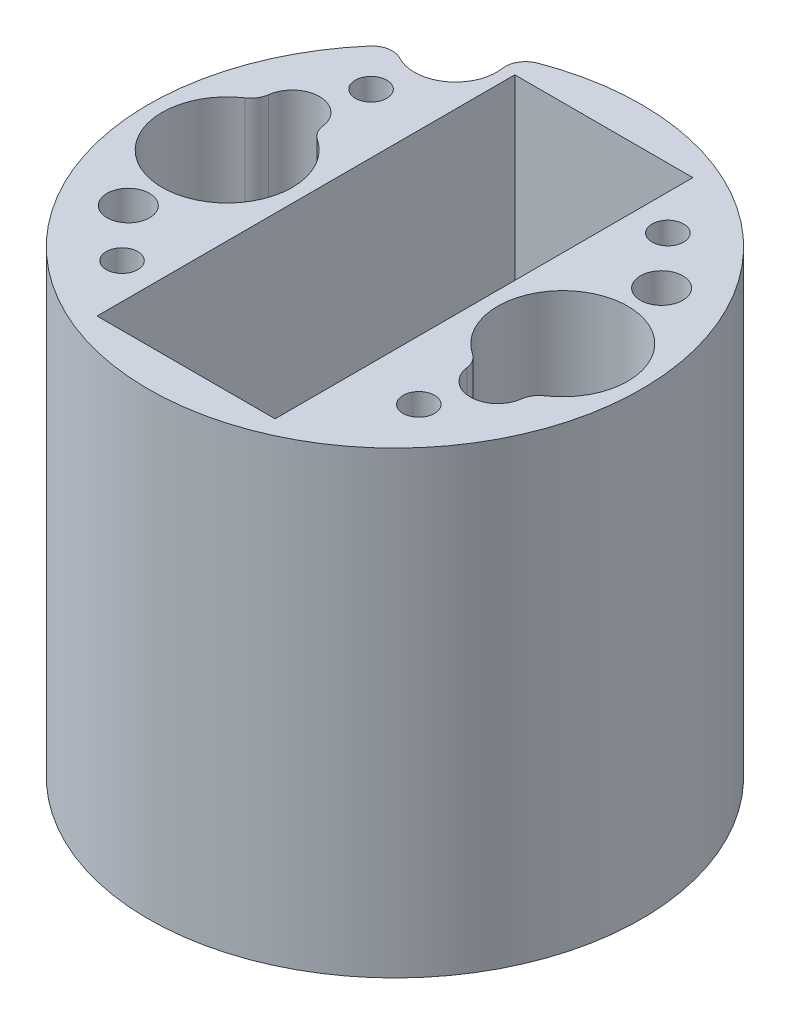
SolidWorks part; units mm, degrees
ref_plane "Front Plane" through (0, 0, 0) normal (0, 0, 1) x (1, 0, 0)
ref_plane "Top Plane" through (0, 0, 0) normal (0, 1, 0) x (1, 0, 0)
ref_plane "Right Plane" through (0, 0, 0) normal (1, 0, 0) x (0, 0, -1)
sketch "Sketch1" plane through (0, 0, 0) normal (0, 1, 0) x (1, 0, 0)
  line L0 (-13, 30.5) -> (13, -30.5) construction
  line L1 (-13, 30.5) -> (13, 30.5)
  line L2 (-13, 30.5) -> (-13, -30.5)
  line L3 (-13, -30.5) -> (13, -30.5)
  line L4 (13, 30.5) -> (13, -30.5)
  line L5 (-24.5, 0) -> (24.5, 0) construction
  line L6 (-34, 0) -> (-36, 0) construction
  line L7 (34, 0) -> (36, 0) construction
  line L8 (-15, 0) -> (-13, 0) construction
  circle A0 centre (0, 0) radius 36
  circle A3 centre (-24.5, 0) radius 9.5
  circle A4 centre (24.5, 0) radius 9.5
  point P5 (0, 0)
  point P12 (0, 0)
  dimension "D1" = 72
  dimension "D2" = 61
  dimension "D4" = 19
  dimension "D3" = 26
extrude "Boss-Extrude1" add sketch "Sketch1" along normal blind 64
sketch "Sketch2" plane through (0, 0, 0) normal (0, -1, 0) x (1, 0, 0)
  circle A0 centre (0, 0) radius 36
extrude "Boss-Extrude2" add sketch "Sketch2" along normal blind 3
extrude "Boss-Extrude3" add sketch "Sketch1<2>" along normal blind 16 contours A3 | A4 region at (-24.5, 0, 0) region at (24.5, 0, 0)
sketch "Sketch1<2>" plane through (0, 0, 0) normal (0, 1, 0) x (1, 0, 0) same geometry as "Sketch1"
sketch "Sketch4" plane through (0, 64, 0) normal (0, 1, 0) x (1, 0, 0)
  line L0 (-24.5, 9.5) -> (-24.5, 0) construction
  line L1 (-24.5, 0) -> (24.5, 0) construction
  line L2 (24.5, 0) -> (24.5, -9.5) construction
  line L3 (-24.5, 9.5) -> (-1.5428, 9.5) construction
  circle A0 centre (-24.5, 9.5) radius 4
  circle A1 centre (-24.5, 0) radius 9.5 construction
  circle A2 centre (-24.5, 0) radius 9.5 construction
  circle A3 centre (24.5, -9.5) radius 4
  circle A4 centre (24.5, 0) radius 9.5 construction
  circle A5 centre (24.5, 0) radius 9.5 construction
  dimension "D1" = 8
extrude "Cut-Extrude1" cut sketch "Sketch4" against normal up to surface (48 mm away) up to face at (-24.5, 16, 9.5)
sketch "Sketch5" plane through (0, 64, 0) normal (0, 1, 0) x (1, 0, 0)
  line L0 (0, 0) -> (20.0764, 0) construction
  line L1 (-18.1808, -21.667) -> (21.667, -18.1808) construction
  line L2 (-18.1808, -21.667) -> (-21.667, 18.1808) construction
  line L3 (-21.667, 18.1808) -> (18.1808, 21.667) construction
  line L4 (21.667, -18.1808) -> (18.1808, 21.667) construction
  line L5 (-18.1808, -21.667) -> (18.1808, 21.667) construction
  line L6 (-21.667, 18.1808) -> (21.667, -18.1808) construction
  circle A0 centre (-21.667, 18.1808) radius 1.5
  circle A1 centre (-18.1808, -21.667) radius 1.5
  circle A2 centre (21.667, -18.1808) radius 1.5
  circle A3 centre (18.1808, 21.667) radius 1.5
  circle A4 centre (-21.667, 18.1808) radius 2.3
  circle A5 centre (18.1808, 21.667) radius 2.3
  circle A6 centre (21.667, -18.1808) radius 2.3
  circle A7 centre (-18.1808, -21.667) radius 2.3
  point P0 (0, 0)
  dimension "D2" = 3
  dimension "D3" = 4.6
  dimension "D1" = 40
  dimension "D4" = 85
extrude "Cut-Extrude2" cut sketch "Sketch5" against normal blind 20 contours A0 | A3 | A1 | A2 region at (-21.667, 64, -18.1808) region at (-18.1808, 64, 21.667) region at (21.667, 64, 18.1808) region at (18.1808, 64, -21.667)
extrude "Cut-Extrude3" cut sketch "Sketch5<3>" against normal blind 6
sketch "Sketch5<3>" plane through (0, 64, 0) normal (0, 1, 0) x (1, 0, 0) same geometry as "Sketch5"
sketch "Sketch6" plane through (0, 64, 0) normal (0, 1, 0) x (1, 0, 0)
  line L0 (-24.6817, -14.25) -> (24.6817, 14.25) construction
  line L1 (0, 0) -> (24.909, 0) construction
  circle A0 centre (-24.6817, -14.25) radius 3.1
  circle A1 centre (24.6817, 14.25) radius 3.1
  point P4 (0, 0)
  dimension "D1" = 6.2
  dimension "D2" = 57
  dimension "D3" = 30
extrude "Cut-Extrude4" cut sketch "Sketch6" against normal through all both and the other way through all
sketch "Sketch7" plane through (0, 64, 0) normal (0, 1, 0) x (1, 0, 0)
  line L0 (-20.6488, 29.4895) -> (0, 0) construction
  line L1 (0, 0) -> (0, 21.7628) construction
  arc A0 (-25.2598, 25.6504) -> (-15.4641, 32.5094) centre (-20.6488, 29.4895) ccw
  circle A1 centre (0, 0) radius 36 construction
  arc A2 (-15.4641, 32.5094) -> (-25.2598, 25.6504) centre (0, 0) ccw
  dimension "D1" = 6
  dimension "D2" = 35
extrude "Cut-Extrude5" cut sketch "Sketch7" against normal through all both
fillet "Fillet1" radius 3 6 edges at (28.4104, 40, 8.6579) (20.5896, 40, 8.6579) (-20.5896, 40, -8.6579) (-28.4104, 40, -8.6579) (-15.4641, 30.5, -32.5094) (-25.2598, 30.5, -25.6504)
